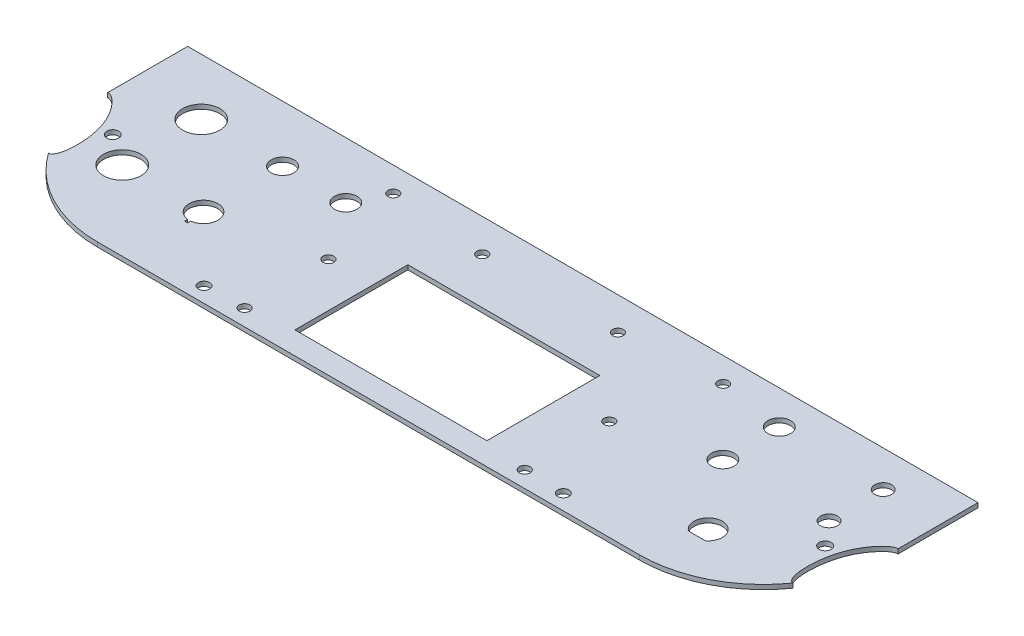
SolidWorks part; units mm, degrees
material "Thornel Mat VMA"
ref_plane "Front Plane" through (0, 0, 0) normal (0, 0, 1) x (1, 0, 0)
ref_plane "Top Plane" through (0, 0, 0) normal (0, 1, 0) x (1, 0, 0)
ref_plane "Right Plane" through (0, 0, 0) normal (1, 0, 0) x (0, 0, -1)
sketch "Sketch1" plane through (0, 0, 0) normal (0, 1, 0) x (1, 0, 0)
  line L13 (-222.25, 0) -> (222.25, 0) construction
  line L14 (222.25, -14.6125) -> (222.25, 36.1875)
  line L15 (222.25, 36.1875) -> (-222.25, 36.1875)
  line L16 (-222.25, -14.6125) -> (-222.25, 36.1875)
  line L18 (0, -95.4736) -> (0, 95.4736) construction
  line L19 (152.4, -84.4625) -> (-152.4, -84.4625)
  arc A0 (222.25, -14.6125) -> (152.4, -84.4625) centre (152.4, -14.6125) cw
  arc A1 (-152.4, -84.4625) -> (-222.25, -14.6125) centre (-152.4, -14.6125) cw
  point P10 (0, 0)
  point P16 (0, 0)
  point P17 (0, -84.4625)
  dimension "D1" = 50.8
  dimension "D2" = 444.5
  dimension "D3" = 304.8
  dimension "D5" = 120.65
  dimension "D6" = 36.1875
extrude "Boss-Extrude1" add sketch "Sketch1" along normal blind 2.54
sketch "Sketch2" plane through (0, 2.54, 0) normal (0, 1, 0) x (1, 0, 0)
  line L1 (53.975, -71.7625) -> (-53.975, -71.7625)
  line L2 (53.975, -71.7625) -> (53.975, -8.2625)
  line L3 (53.975, -8.2625) -> (-53.975, -8.2625)
  line L4 (-53.975, -71.7625) -> (-53.975, -8.2625)
  line L5 (53.975, -71.7625) -> (-53.975, -8.2625) construction
  line L6 (53.975, -8.2625) -> (-53.975, -71.7625) construction
  line L8 (-152.4, -84.4625) -> (152.4, -84.4625) construction
  point P0 (0, -40.0125)
  dimension "D1" = 63.5
  dimension "D2" = 12.7
  dimension "D3" = 107.95
extrude "Cut-Extrude1" cut sketch "Sketch2" against normal through all
sketch "Sketch4" plane through (0, 2.54, 0) normal (0, 1, 0) x (1, 0, 0)
  line L6 (-138.01, -48.0677) -> (-138.01, -49.8125)
  line L12 (-138.01, -49.8125) -> (-136.31, -49.8125)
  line L14 (-136.31, -49.8125) -> (-136.31, -48.0677)
  line L17 (222.25, -14.6125) -> (222.25, 36.1875) construction
  line L18 (222.25, 36.1875) -> (-222.25, 36.1875) construction
  line L19 (-222.25, 36.1875) -> (-222.25, -14.6125) construction
  line L21 (164.1475, -59.0625) -> (154.6225, -59.0625)
  line L22 (-152.4, -84.4625) -> (152.4, -84.4625) construction
  line L54 (87.5424, -0.6073) -> (87.4312, -0.6714)
  circle A0 centre (189.23, 15.8675) radius 4.7625
  circle A2 centre (-137.16, 4.4375) radius 6.35
  circle A3 centre (129.54, 17.1375) radius 6.35
  circle A4 centre (129.54, -14.6125) radius 6.35
  circle A6 centre (189.23, -14.6125) radius 4.7625
  circle A7 centre (-182.88, -40.0125) radius 10.5
  arc A8 (-136.31, -48.0677) -> (-138.01, -48.0677) centre (-137.16, -40.0125) ccw
  circle A9 centre (-182.88, 4.4375) radius 10.5
  arc A12 (164.1475, -59.0625) -> (154.6225, -59.0625) centre (159.385, -52.7125) ccw
  circle A25 centre (-101.6, 4.4375) radius 6.35
  circle A36 centre (-38.131, 17.7452) radius 3.025 construction
  circle A37 centre (-79, -27.9475) radius 3.025 construction
  circle A48 centre (-78.7827, -75.2875) radius 3.025 construction
  circle A49 centre (78.7827, -75.2875) radius 3.025 construction
  circle A51 centre (79, -27.9475) radius 3.025 construction
  arc A72 (85, -6.1987) -> (84.9641, -5.581) centre (79.666, -6.1987) ccw
  circle A73 centre (38.131, 17.7452) radius 3.025 construction
  circle A74 centre (-38.131, 17.7452) radius 3.025
  circle A75 centre (-79, -27.9475) radius 3.025
  circle A76 centre (-78.7827, -75.2875) radius 3.025
  circle A77 centre (78.7827, -75.2875) radius 3.025
  circle A78 centre (79, -27.9475) radius 3.025
  circle A79 centre (38.131, 17.7452) radius 3.025
  point P24 (-137.16, -49.8125)
  dimension "D2" = 12.7
  dimension "D3" = 15.875
  dimension "D11" = 9.8
  dimension "D12" = 16.2
  dimension "D20" = 31.75
  dimension "D25" = 9.525
  dimension "D10" = 21
  dimension "D4" = 31.75
  dimension "D5" = 20.32
  dimension "D6" = 33.02
  dimension "D7" = 59.69
  dimension "D8" = 35.56
  dimension "D9" = 50.8
  dimension "D13" = 39.37
  dimension "D14" = 85.09
  dimension "D15" = 62.865
  dimension "D16" = 31.75
  dimension "D17" = 76.2
  dimension "D18" = 6.35
  dimension "D19" = 1.7
  dimension "D21" = 31.75
sketch "Sketch5" plane through (0, 2.54, 0) normal (0, 1, 0) x (1, 0, 0)
  line L0 (222.25, -14.6125) -> (222.25, 36.1875) construction
  line L1 (0, -1.397) -> (0, 1.397) construction
  arc A0 (152.4, -84.4625) -> (222.25, -14.6125) centre (152.4, -14.6125) ccw construction
  spline S0 degree 3 poles (235.1366, 7.4285) (207.1804, -83.7935) (202.3049, -25.2668) (235.1366, 7.4285) (207.1804, -83.7935) (202.3049, -25.2668) knots -1 -0.674196 -0.483325 0 0.325804 0.516675 1 1.325804 1.516675 2 only from (209.4403, -54.9291) to (209.4403, -54.9291)
  spline S1 degree 3 poles (-235.1366, 7.4285) (-207.1804, -83.7935) (-202.3049, -25.2668) (-235.1366, 7.4285) (-207.1804, -83.7935) (-202.3049, -25.2668) knots -1 -0.674196 -0.483325 0 0.325804 0.516675 1 1.325804 1.516675 2 only from (-209.4403, -54.9291) to (-209.4403, -54.9291)
  line M8 (-222.25, 36.1875) -> (-222.25, -14.6125)
  arc M9 (-222.25, -14.6125) -> (-152.4, -84.4625) centre (-152.4, -14.6125) ccw
extrude "Cut-Extrude4" cut sketch "Sketch5" against normal up to surface (2.54 mm away) contours S1 M9 M8 | S0 region at (-213.6132, 2.54, 31.5069) up to face at (0, 0, 40.0125)
extrude "Cut-Extrude3" cut sketch "Sketch4" against normal through all contours A25 | A77 | A9 | A8 L6 L12 L14 | A7 | A6 | A0 | A3 | A2 | A12 L21 | A4 | A79 | A78 | A74 | A75 | A76 region at (-101.6, 2.54, -4.4375) region at (78.7827, 2.54, 75.2875)
sketch "Sketch6" plane through (0, 0, 0) normal (0, -1, 0) x (1, 0, 0)
  line L0 (0, -1.397) -> (0, 1.397) construction
  circle A0 centre (92.7683, -22.3351) radius 3.0138
  circle A1 centre (101.0562, 75.863) radius 3.1768
  circle A2 centre (200.3502, 27.8837) radius 3.3788
  circle A3 centre (-92.7683, -22.3351) radius 3.0138
  circle A4 centre (-200.3502, 27.8837) radius 3.3788
  circle A5 centre (-101.0562, 75.863) radius 3.1768
  point P14 (200.3502, 27.8837)
  point P15 (0, 0)
extrude "Cut-Extrude5" cut sketch "Sketch6" against normal through all
